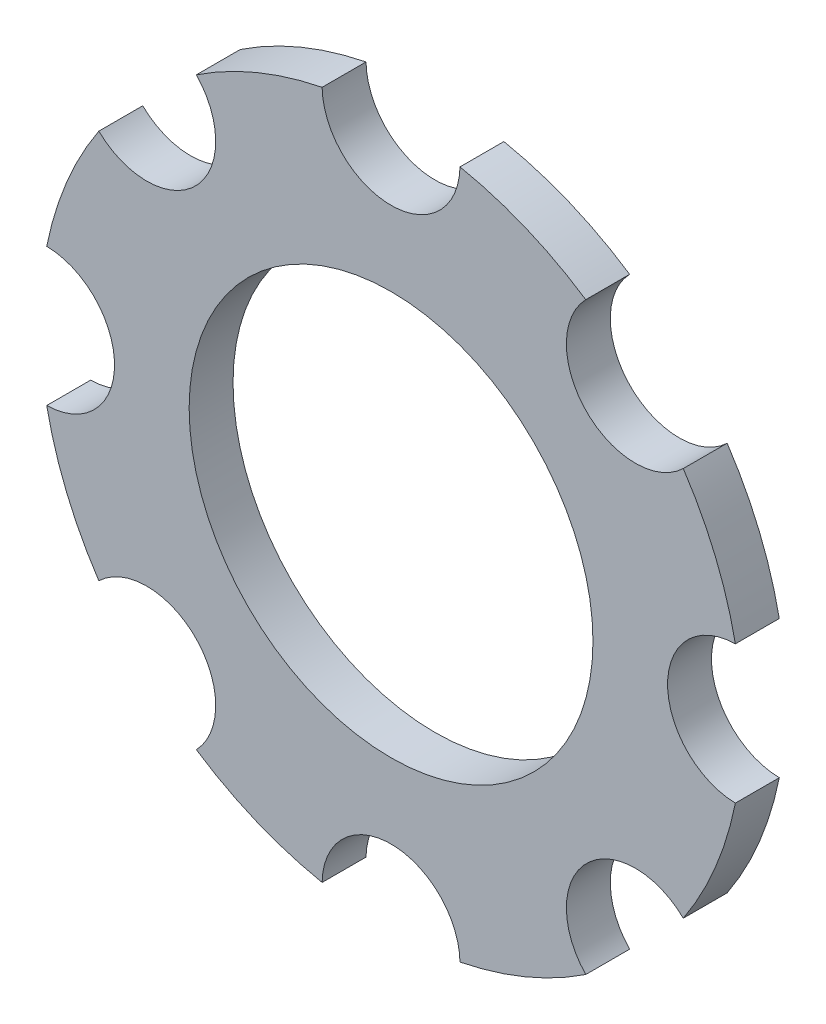
SolidWorks part; units mm, degrees
ref_plane "Front" through (0, 0, 0) normal (0, 0, 1) x (1, 0, 0)
ref_plane "Top" through (0, 0, 0) normal (0, 1, 0) x (1, 0, 0)
ref_plane "Right" through (0, 0, 0) normal (1, 0, 0) x (0, 0, -1)
sketch "Sketch1" plane through (0, 0, 0) normal (0, 0, 1) x (1, 0, 0)
  circle A0 centre (0, 0) radius 4
  circle A1 centre (0, 0) radius 2.3
extrude "Base-Extrude" add sketch "Sketch1" against normal blind 0.5
sketch "Sketch2" plane through (-1.6093, -2.55, 0) normal (0, 0, 1) x (1, 0, 0)
  line L0 (1.6093, 2.55) -> (9.6093, 2.55) construction
  line L1 (1.6093, 2.55) -> (1.6093, 4.3896) construction
  line L2 (0.8239, 16.4854) -> (0.8239, 6.4854)
  line L3 (2.3947, 6.4854) -> (2.3947, 16.4854)
  line L4 (2.3947, 16.4854) -> (0.8239, 16.4854)
  circle A0 centre (1.6093, 2.55) radius 3.15 construction
  circle A1 centre (1.6093, 2.55) radius 2.3 construction
  arc A2 (2.3947, 6.4854) -> (0.8239, 6.4854) centre (1.6093, 6.4854) cw
  dimension "D2" = 6.3
  dimension "D1" = 8
  dimension "D3" = 1.5708
  dimension "D4" = 10
extrude "TypeASlot" cut sketch "Sketch2" against normal through all
pattern_circular "TypeAPattern" count 8 over 360 about axis through (0, 0, -0.5) along (0, 0, 1) of "TypeASlot"
equation "\"D2@Sketch2\" =  ( \"D0@Sketch1\" + \"d@Sketch1\" )  / 2"
equation "\"D3@Sketch2\" = \"D0@Sketch1\" * 3.14159 / \"D1@Sketch2\" / 2"
